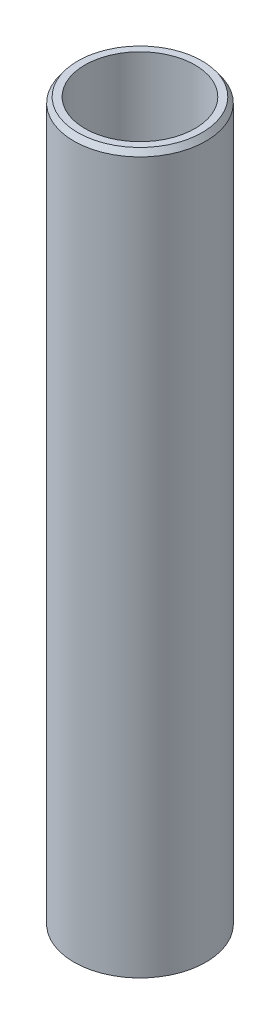
SolidWorks part; units mm, degrees
ref_plane "Front Plane" through (0, 0, 0) normal (0, 0, 1) x (1, 0, 0)
ref_plane "Top Plane" through (0, 0, 0) normal (0, 1, 0) x (1, 0, 0)
ref_plane "Right Plane" through (0, 0, 0) normal (1, 0, 0) x (0, 0, -1)
sketch "Sketch1" plane through (0, 0, 0) normal (0, 1, 0) x (1, 0, 0)
  circle A0 centre (0, 0) radius 55
  dimension "SHAFT_OD" = 110
extrude "Boss-Extrude1" add sketch "Sketch1" along normal blind 600
sketch "Sketch2" plane through (0, 0, 0) normal (0, 1, 0) x (1, 0, 0)
  circle A0 centre (0, 0) radius 45.8765
  dimension "BORE_D" = 91.753
extrude "Cut-Extrude1" cut sketch "Sketch2" along normal through all
chamfer "Chamfer1" distance 4.535 angle 35.524 2 edges at (0, 600, 55) (0, 0, 55) first distance on face at (0, 600, 55) first distance on face at (0, 0, 45.8765)
